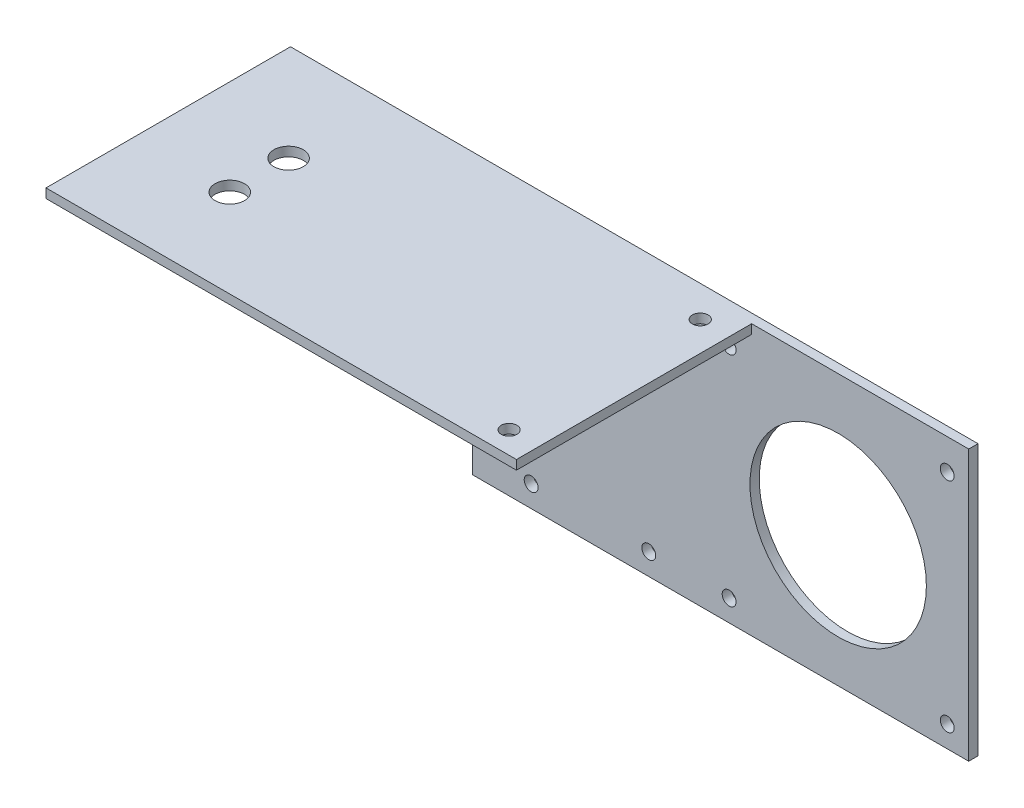
SolidWorks part; units mm, degrees
ref_plane "Front Plane" through (0, 0, 0) normal (0, 0, 1) x (1, 0, 0)
ref_plane "Top Plane" through (0, 0, 0) normal (0, 1, 0) x (1, 0, 0)
ref_plane "Right Plane" through (0, 0, 0) normal (1, 0, 0) x (0, 0, -1)
sketch "Sketch1" plane through (0, 0, 0) normal (0, 0, 1) x (1, 0, 0)
  line L0 (102.55, 51.75) -> (12.7, 51.75) construction
  line L1 (0, 58.4) -> (107.2, 58.4)
  line L2 (0, 58.4) -> (0, 0)
  line L3 (0, 0) -> (107.2, 0)
  line L4 (107.2, 58.4) -> (107.2, 0)
  line L5 (102.55, 51.75) -> (102.55, 4.65) construction
  line L6 (12.7, 51.75) -> (12.7, 4.65) construction
  line L7 (55.45, 4.65) -> (55.45, 51.75) construction
  line L8 (12.7, 4.65) -> (102.55, 4.65) construction
  line L9 (38.1, 51.75) -> (38.1, 4.65) construction
  line L10 (55.45, 51.75) -> (102.55, 4.65) construction
  line L11 (102.55, 51.75) -> (55.45, 4.65) construction
  circle A0 centre (102.55, 51.75) radius 1.5
  circle A1 centre (102.55, 4.65) radius 1.5
  circle A2 centre (55.45, 4.65) radius 1.5
  circle A3 centre (55.45, 51.75) radius 1.5
  circle A4 centre (12.7, 51.75) radius 1.5
  circle A5 centre (38.1, 51.75) radius 1.5
  circle A6 centre (12.7, 4.65) radius 1.5
  circle A7 centre (38.1, 4.65) radius 1.5
  circle A8 centre (79, 28.2) radius 19.05
  dimension "D3" = 3
  dimension "D10" = 38.1
  dimension "D1" = 58.4
  dimension "D2" = 107.2
  dimension "D4" = 47.1
  dimension "D5" = 47.1
  dimension "D6" = 4.65
  dimension "D7" = 25.4
  dimension "D8" = 4.65
  dimension "D9" = 12.7
extrude "Boss-Extrude1" add sketch "Sketch1" against normal blind 2
sketch "Sketch2" plane through (0, 0, -2) normal (0, 0, -1) x (-1, 0, 0)
  line L0 (0, 58.4) -> (41.275, 58.4)
  line L1 (0, 58.4) -> (0, 0) construction
  line L2 (0, 56.4) -> (-60.325, 56.4)
  line L3 (-60.325, 56.4) -> (-60.325, 58.4)
  line L4 (-107.2, 58.4) -> (0, 58.4) construction
  line L5 (-60.325, 58.4) -> (0, 58.4)
  line L6 (41.275, 58.4) -> (41.275, 56.4)
  line L7 (41.275, 56.4) -> (0, 56.4)
  dimension "D1" = 60.325
  dimension "D2" = 2
  dimension "D3" = 41.275
extrude "Boss-Extrude2" add sketch "Sketch2" against normal blind 52.8
sketch "Sketch3" plane through (0, 58.4, 0) normal (0, 1, 0) x (1, 0, 0)
  line L0 (53.975, -4.7625) -> (53.975, -46.0375) construction
  line L2 (60.325, -50.8) -> (60.325, 0) construction
  line L3 (-41.275, -50.8) -> (60.325, -50.8) construction
  circle A0 centre (53.975, -4.7625) radius 1.7
  circle A1 centre (53.975, -46.0375) radius 1.7
  dimension "D1" = 3.4
  dimension "D2" = 41.275
  dimension "D3" = 4.7625
  dimension "D4" = 6.35
extrude "Cut-Extrude1" cut sketch "Sketch3" against normal through all
sketch "Sketch4" plane through (0, 58.4, 0) normal (0, 1, 0) x (1, 0, 0)
  line L0 (-20.6375, 2) -> (-20.6375, -50.8) construction
  line L1 (107.2, 2) -> (-41.275, 2) construction
  line L2 (-41.275, -50.8) -> (60.325, -50.8) construction
  line L3 (-41.275, -50.8) -> (-41.275, 2) construction
  circle A0 centre (-20.6375, -19.05) radius 3.175
  circle A1 centre (-20.6375, -31.75) radius 3.175
  dimension "D2" = 6.35
  dimension "D3" = 6.35
  dimension "D1" = 20.6375
  dimension "D4" = 12.7
  dimension "D5" = 19.05
extrude "Cut-Extrude2" cut sketch "Sketch4" against normal blind 10
